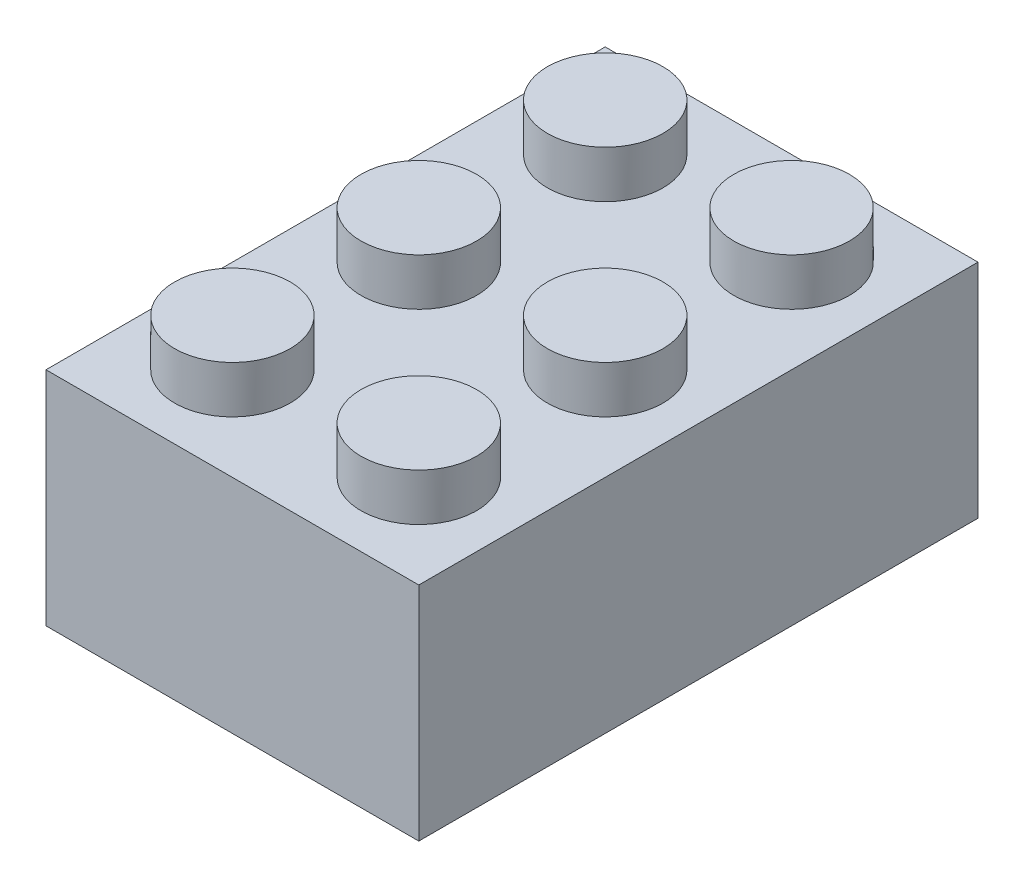
SolidWorks part; units mm, degrees
ref_plane "Front Plane" through (0, 0, 0) normal (0, 0, 1) x (1, 0, 0)
ref_plane "Top Plane" through (0, 0, 0) normal (0, 1, 0) x (1, 0, 0)
ref_plane "Right Plane" through (0, 0, 0) normal (1, 0, 0) x (0, 0, -1)
sketch "stencil" plane through (0, 0, 0) normal (0, 1, 0) x (1, 0, 0)
  line L2 (14.35, 22.25) -> (1.45, 22.25)
  line L29 (15.75, 23.65) -> (0.05, 23.65)
  line L37 (15.75, 23.65) -> (15.75, 0.05)
  line L38 (15.75, 0.05) -> (0.05, 0.05)
  line L39 (0.05, 23.65) -> (0.05, 0.05)
  line L40 (7.9, 0.05) -> (7.9, 23.65) construction
  line L41 (15.75, 11.85) -> (0.05, 11.85) construction
  line L50 (1.45, 22.25) -> (1.45, 1.45)
  line L51 (14.35, 1.45) -> (1.45, 1.45)
  line L52 (14.35, 22.25) -> (14.35, 1.45)
  circle A43 centre (3.95, 3.95) radius 2.45
  circle A44 centre (7.9, 7.9) radius 3.2
  circle A46 centre (3.95, 11.85) radius 2.45
  circle A47 centre (7.9, 15.8) radius 3.2
  circle A49 centre (3.95, 19.75) radius 2.45
  circle A50 centre (11.85, 19.75) radius 2.45
  circle A51 centre (11.85, 11.85) radius 2.45
  circle A52 centre (11.85, 3.95) radius 2.45
  circle A53 centre (7.9, 15.8) radius 2.4
  circle A54 centre (7.9, 7.9) radius 2.4
  point P1 (0, 0)
  point P6 (3.95, -15.8)
  point P9 (7.9, -15.8)
  point P10 (7.9, -11.85)
  point P13 (3.95, -7.9)
  point P15 (7.9, -7.9)
  point P17 (7.9, -3.95)
  point P18 (3.95, 0)
  point P21 (7.9, 0)
  point P25 (7.9, 3.95)
  point P27 (3.95, 7.9)
  point P28 (7.9, 7.9)
  point P29 (0, -11.85)
  point P30 (0, -7.9)
  point P31 (0, 3.95)
  point P34 (0, -3.95)
  point P35 (3.95, 0)
  point P36 (0, 15.8)
  point P37 (0, 23.7)
  point P38 (7.9, 23.7)
  point P39 (15.8, 23.7)
  point P40 (15.8, 15.8)
  point P41 (15.8, 7.9)
  point P48 (15.8, 0)
  point P49 (7.9, 0)
  point P51 (11.85, 0)
  point P52 (3.95, 3.95)
  point P53 (7.9, 3.95)
  point P55 (11.85, 3.95)
  point P56 (3.95, 7.9)
  point P57 (7.9, 7.9)
  point P58 (11.85, 7.9)
  point P59 (3.95, 11.85)
  point P60 (7.9, 11.85)
  point P61 (11.85, 11.85)
  point P64 (3.95, 15.8)
  point P65 (7.9, 15.8)
  point P66 (11.85, 15.8)
  point P68 (3.95, 19.75)
  point P69 (7.9, 19.75)
  point P70 (11.85, 19.75)
  point P71 (0, 3.95)
  point P73 (0, 7.9)
  point P75 (0, 11.85)
  point P77 (0, 15.8)
  point P79 (0, 19.75)
  point P81 (15.8, 3.95)
  point P83 (15.8, 7.9)
  point P85 (15.8, 11.85)
  point P87 (15.8, 15.8)
  point P88 (15.8, 19.75)
  point P91 (0, 23.7)
  point P93 (3.95, 23.7)
  point P94 (7.9, 23.7)
  point P95 (11.85, 23.7)
  point P96 (15.8, 23.7)
  point P97 (7.9, 11.85)
  point P118 (7.9, 11.85)
  dimension "D5" = 4.9
  dimension "D7" = 6.4
  dimension "D3" = 3.95
  dimension "D4" = 3.95
  dimension "D9" = 23.6
  dimension "D10" = 15.7
  dimension "D6" = 0.8
  dimension "D8" = 0.8
  dimension "D11" = 1.4
  dimension "D1" = 5
  dimension "D2" = 7
sketch "Sketch1" plane through (0, 0, 0) normal (0, 1, 0) x (1, 0, 0)
  line L9 (15.8, 23.7) -> (0, 23.7)
  line L10 (15.8, 23.7) -> (15.8, 0)
  line L11 (15.8, 0) -> (0, 0)
  line L12 (0, 23.7) -> (0, 0)
  line L13 (7.9, 0) -> (7.9, 23.7) construction
  line L14 (15.8, 11.85) -> (0, 11.85) construction
  point P0 (7.9, 11.85)
extrude "Boss-Extrude1" add sketch "Sketch1" along normal mid plane 9.4
sketch "Sketch2" plane through (0, 4.7, 0) normal (0, 1, 0) x (1, 0, 0)
  circle A14 centre (3.95, 3.95) radius 2.45
  circle A15 centre (11.85, 3.95) radius 2.45
  circle A16 centre (11.85, 11.85) radius 2.45
  circle A17 centre (3.95, 11.85) radius 2.45
  circle A18 centre (3.95, 19.75) radius 2.45
  circle A19 centre (11.85, 19.75) radius 2.45
  circle A20 centre (3.95, 3.95) radius 2.45 construction
extrude "Boss-Extrude2" add sketch "Sketch2" along normal blind 2
sketch "Sketch4" plane through (0, -4.7, 0) normal (0, -1, 0) x (1, 0, 0)
  line L5 (14.35, -22.25) -> (1.45, -22.25)
  line L7 (14.35, -22.25) -> (14.35, -1.45)
  line L11 (14.35, -1.45) -> (1.45, -1.45)
  line L12 (1.45, -22.25) -> (1.45, -1.45)
  line L13 (7.9, -1.45) -> (7.9, -22.25) construction
  line L14 (14.35, -11.85) -> (1.45, -11.85) construction
  point P0 (7.9, -11.85)
extrude "Cut-Extrude1" cut sketch "Sketch4" against normal blind 4
sketch "Sketch5" plane through (0, -0.7, 0) normal (0, -1, 0) x (1, 0, 0)
  circle A1 centre (7.9, -7.9) radius 2.4
  circle A5 centre (7.9, -15.8) radius 2.4
  circle A12 centre (7.9, -15.8) radius 3.2
  circle A13 centre (7.9, -7.9) radius 3.2
  circle A14 centre (7.9, -15.8) radius 2.4 construction
  circle A15 centre (7.9, -7.9) radius 3.2 construction
extrude "Boss-Extrude3" add sketch "Sketch5" along normal up to surface (4 mm away) up to face at (7.9, -4.7, -11.85)
equation "\"t\" = 0.10'tolerance"
equation "\"D9@stencil\"=23.70-\"t\""
equation "\"D10@stencil\"=15.80-\"t\""
equation "\"D11@stencil\"=1.50-\"t\""
equation "\"D7@stencil\"=6.50-\"t\""
equation "\"D1@Boss-Extrude1\"=9.5-\"t\""
